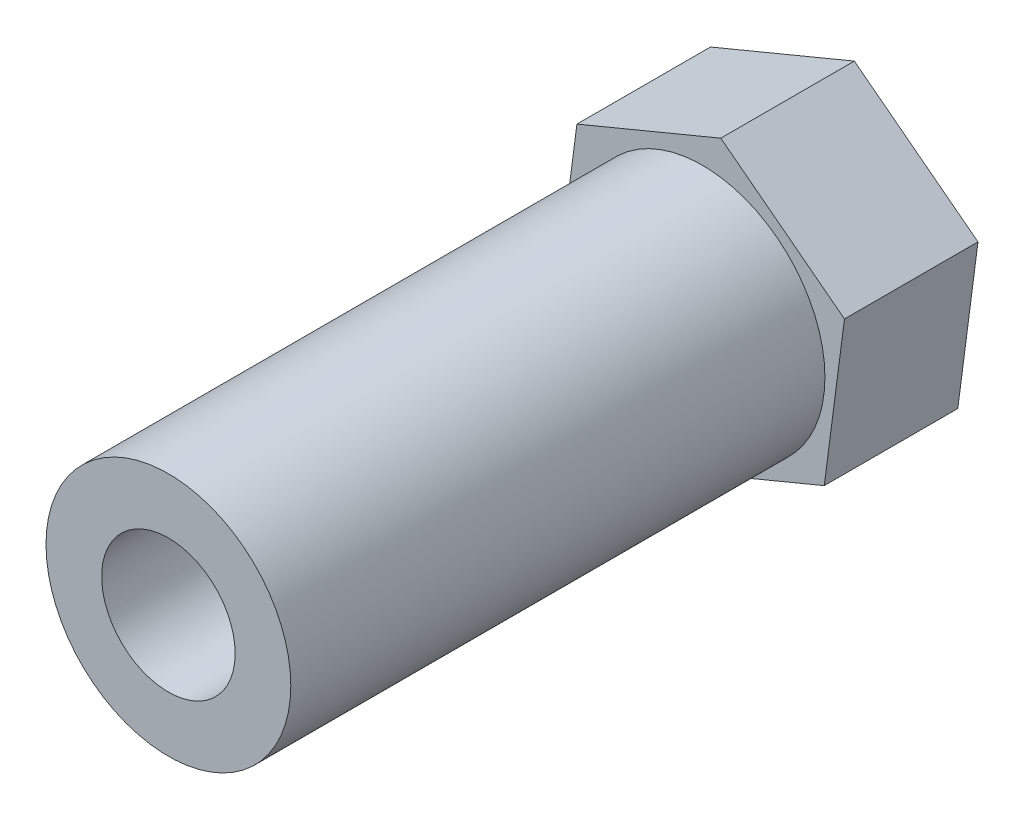
SolidWorks part; units mm, degrees
ref_plane "Front Plane" through (0, 0, 0) normal (0, 0, 1) x (1, 0, 0)
ref_plane "Top Plane" through (0, 0, 0) normal (0, 1, 0) x (1, 0, 0)
ref_plane "Right Plane" through (0, 0, 0) normal (1, 0, 0) x (0, 0, -1)
sketch "Sketch1" plane through (0, 0, 0) normal (0, 0, 1) x (1, 0, 0)
  line L1 (1.0074, -2.3072) -> (1.9156, 4.6336)
  line L2 (1.9156, 4.6336) -> (-3.6412, 8.8906)
  line L3 (-3.6412, 8.8906) -> (-10.1063, 6.2067)
  line L4 (-10.1063, 6.2067) -> (-11.0145, -0.7341)
  line L5 (-11.0145, -0.7341) -> (-5.4577, -4.9911)
  line L6 (-5.4577, -4.9911) -> (1.0074, -2.3072)
  circle A0 centre (-4.5494, 1.9498) radius 6.0622 construction
  dimension "D1" = 7
extrude "Boss-Extrude1" add sketch "Sketch1" along normal blind 6
sketch "Sketch3" plane through (0, 0, 6) normal (0, 0, 1) x (1, 0, 0)
  circle A0 centre (-4.4621, 1.9253) radius 5.5
  dimension "D1" = 11
extrude "Boss-Extrude2" add sketch "Sketch3" along normal blind 24
sketch "Sketch4" plane through (0, 0, 0) normal (0, 0, -1) x (-1, 0, 0)
  circle A0 centre (4.4621, 1.9253) radius 1.5
  circle A1 centre (4.4621, 1.9253) radius 5.5 construction
  dimension "D1" = 3
  dimension "D2" = 0
extrude "Cut-Extrude1" cut sketch "Sketch4" against normal blind 6
sketch "Sketch5" plane through (0, 0, 30) normal (0, 0, 1) x (1, 0, 0)
  circle A0 centre (-4.4621, 1.9253) radius 3
  circle A2 centre (-4.4621, 1.9253) radius 5.5 construction
  point P4 (-4.4621, 1.7926)
  point P5 (-4.4621, 1.7926)
  dimension "D2" = 6
  dimension "D1" = 0
extrude "Cut-Extrude2" cut sketch "Sketch5" against normal blind 24
